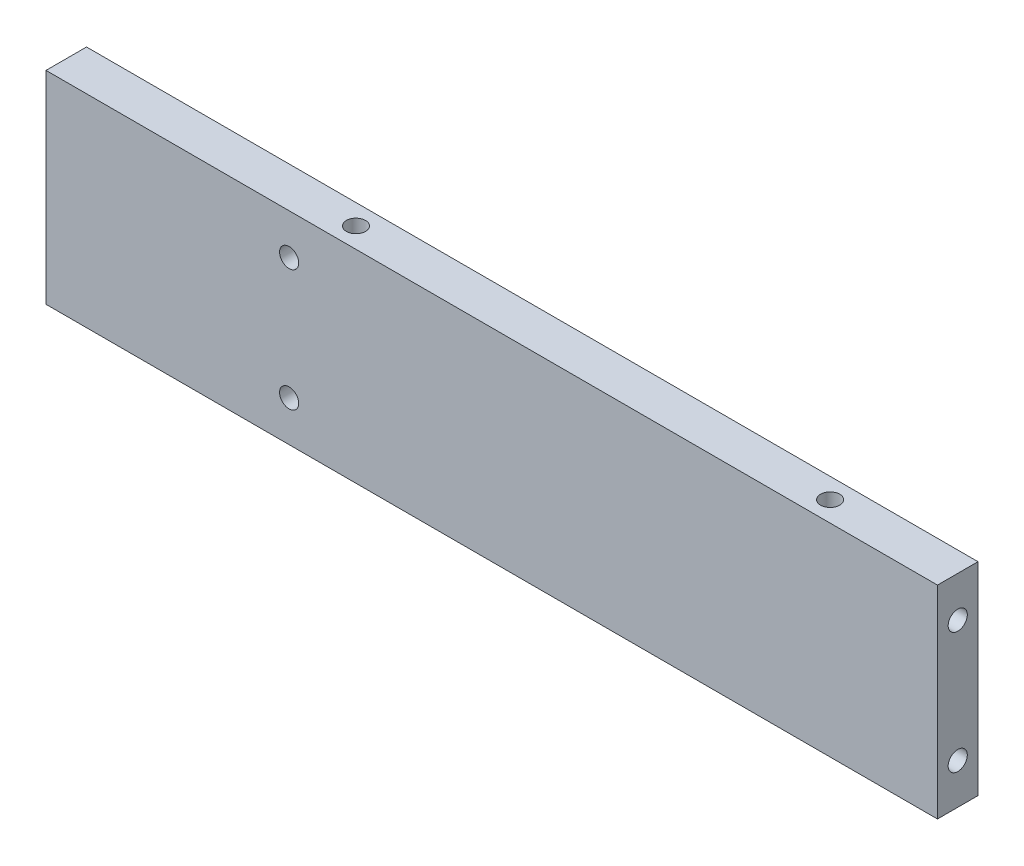
SolidWorks part; units mm, degrees
ref_plane "Front Plane" through (0, 0, 0) normal (0, 0, 1) x (1, 0, 0)
ref_plane "Top Plane" through (0, 0, 0) normal (0, 1, 0) x (1, 0, 0)
ref_plane "Right Plane" through (0, 0, 0) normal (1, 0, 0) x (0, 0, -1)
sketch "top profile" plane through (0, 0, 0) normal (0, 1, 0) x (1, 0, 0)
  line L1 (0, 0) -> (139.7, 0)
  line L2 (0, 0) -> (0, -6.35)
  line L3 (0, -6.35) -> (139.7, -6.35)
  line L4 (139.7, 0) -> (139.7, -6.35)
  dimension "D1" = 139.7
  dimension "D2" = 6.35
extrude "wall mid" add sketch "top profile" along normal blind 31.75 contours L3 L4 L1 L2
sketch "useless but dont delete" plane through (0, 0, 6.35) normal (0, 0, 1) x (1, 0, 0)
  line L1 (0, 28.575) -> (12.7, 28.575) construction
  line L2 (0, 28.575) -> (0, 3.175) construction
  line L3 (0, 3.175) -> (12.7, 3.175) construction
  line L4 (12.7, 28.575) -> (12.7, 3.175) construction
  point P7 (0, 15.875)
  dimension "D1" = 12.7
  dimension "D2" = 15.875
  dimension "D3" = 25.4
sketch "bolt locations" plane through (0, 0, 0) normal (0, 0, 1) x (1, 0, 0)
  line L0 (38.1, 6.35) -> (38.1, 25.4) construction
  line L3 (0, 31.75) -> (139.7, 31.75) construction
  dimension "D1" = 6.35
  dimension "D2" = 6.35
  dimension "D3" = 38.1
hole_wizard "Ø3.0mm Dowel Hole1" positions "Sketch4" profile "Sketch5" hole size "Ø3.0" standard "ANSI Metric" end condition through all
sketch "Sketch4" plane through (0, 0, 0) normal (0, 0, 1) x (1, 0, 0)
  point P0 (38.1, 6.35)
  point P3 (38.1, 25.4)
sketch "Sketch5" plane through (38.1, 6.35, 0) normal (1, 0, 0) x (0, 1, 0)
  line L0 (0, 0) -> (0, 6.35)
  line L1 (0, 6.35) -> (1.5, 6.35)
  line L2 (1.5, 6.35) -> (1.5, 0)
  line L5 (1.5, 0) -> (0, 0)
  line L11 (0, -6.35) -> (0, 107.95) construction
  dimension "Thru Hole Dia." = 3
  dimension "Thru Hole Depth" = 6.35
sketch "Sketch8" plane through (0, 0, 0) normal (0, 0, 1) x (1, 0, 0)
  line L0 (0, 31.75) -> (0, 0) construction
  line L1 (10.16, 28.575) -> (35.56, 28.575)
  line L2 (10.16, 28.575) -> (10.16, 3.175)
  line L3 (10.16, 3.175) -> (35.56, 3.175)
  line L5 (0, 31.75) -> (0, 0) construction
  line L6 (35.56, 20.955) -> (35.56, 28.575)
  line L7 (38.1, 20.955) -> (35.56, 20.955)
  line L8 (38.1, 20.955) -> (38.1, 10.795)
  line L9 (38.1, 10.795) -> (35.56, 10.795)
  line L11 (35.56, 10.795) -> (35.56, 3.175)
  point P6 (0, 15.875)
  point P7 (10.16, 15.875)
  point P12 (38.1, 15.875)
  dimension "D1" = 25.4
  dimension "D2" = 10.16
  dimension "D3" = 35.56
  dimension "D4" = 2.54
  dimension "D5" = 25.4
extrude "motor interferecne" cut sketch "Sketch8" along normal blind 3.81
fillet "Fillet2" radius 5.08 6 edges at (10.16, 3.175, 1.905) (10.16, 28.575, 1.905) (35.56, 3.175, 1.905) (38.1, 10.795, 1.905) (38.1, 20.955, 1.905) (35.56, 28.575, 1.905)
sketch "Sketch9" plane through (0, 0, 0) normal (-1, 0, 0) x (0, 0, 1)
  line L0 (3.175, 6.35) -> (3.175, 25.4) construction
  line L1 (0, 31.75) -> (6.35, 31.75) construction
  dimension "D1" = 3.175
  dimension "D2" = 6.35
  dimension "D3" = 6.35
hole_wizard "Ø3.0mm Dowel Hole2" positions "Sketch12" profile "Sketch13" hole size "Ø3.0" standard "ANSI Metric"
sketch "Sketch12" plane through (0, 0, 0) normal (-1, 0, 0) x (0, 0, 1)
  point P0 (3.175, 25.4)
  point P3 (3.175, 6.35)
sketch "Sketch13" plane through (0, 25.4, 3.175) normal (0, 1, 0) x (0, 0, 1)
  line L0 (0, 0) -> (0, 8.5213)
  line L1 (0, 8.5213) -> (1.5, 7.62)
  line L2 (1.5, 7.62) -> (1.5, 0)
  line L5 (1.5, 0) -> (0, 0)
  line L10 (0, 8.5213) -> (-1.5, 7.62) construction
  line L11 (0, -6.35) -> (0, 107.95) construction
  dimension "Hole Dia." = 3
  dimension "Hole Depth" = 7.62
  dimension "Drill Angle" = 118
ref_plane "Plane1" through (69.85, 0, 0) normal (-1, 0, 0) x (0, 0, 1)
mirror "Mirror1" about plane through (69.85, 0, 0) normal (-1, 0, 0) of "Ø3.0mm Dowel Hole2"
hole_wizard "Ø3.0mm Dowel Hole4" positions "Sketch16" profile "Sketch17" hole size "Ø3.0" standard "ANSI Metric"
sketch "Sketch16" plane through (146.05, 31.75, -25.4) normal (0, 1, 0) x (-1, 0, 0)
  point P0 (26.35, 28.575)
  point P3 (100.65, 28.575)
sketch "Sketch17" plane through (119.7, 31.75, 3.175) normal (1, 0, 0) x (0, 0, 1)
  line L0 (0, 0) -> (0, 7.2513)
  line L1 (0, 7.2513) -> (1.5, 6.35)
  line L2 (1.5, 6.35) -> (1.5, 0)
  line L3 (1.5, 0) -> (0, 0)
  line L4 (0, 7.2513) -> (-1.5, 6.35) construction
  line L5 (0, -6.35) -> (0, 107.95) construction
  dimension "Hole Dia." = 3
  dimension "Hole Depth" = 6.35
  dimension "Drill Angle" = 118
equation "\"width\" = 6in 'side to side 6"
equation "\"height\"= 1.25in'top to bottom from 1.25"
equation "\"length\"=6.25in 'back to front 6.25"
equation "\"side_width\"= 1in"
equation "\"wheel_di\"=1.875in'2.375"
equation "\"wepon_di\" = 1.25in ' milled rectangle must compensate for bolts ~ - .5 1.5"
equation "\"wepon_axle\" = 0.1in ' placement from front .5"
equation "\"frame_bolts\" = 0.125"
equation "\"D1@top profile\" = \"width\" - .5"
equation "\"D2@useless but dont delete\" = \"height\" / 2"
equation "\"D3@useless but dont delete\" = 1"
equation "\"wheel_base\"= 2.5in"
